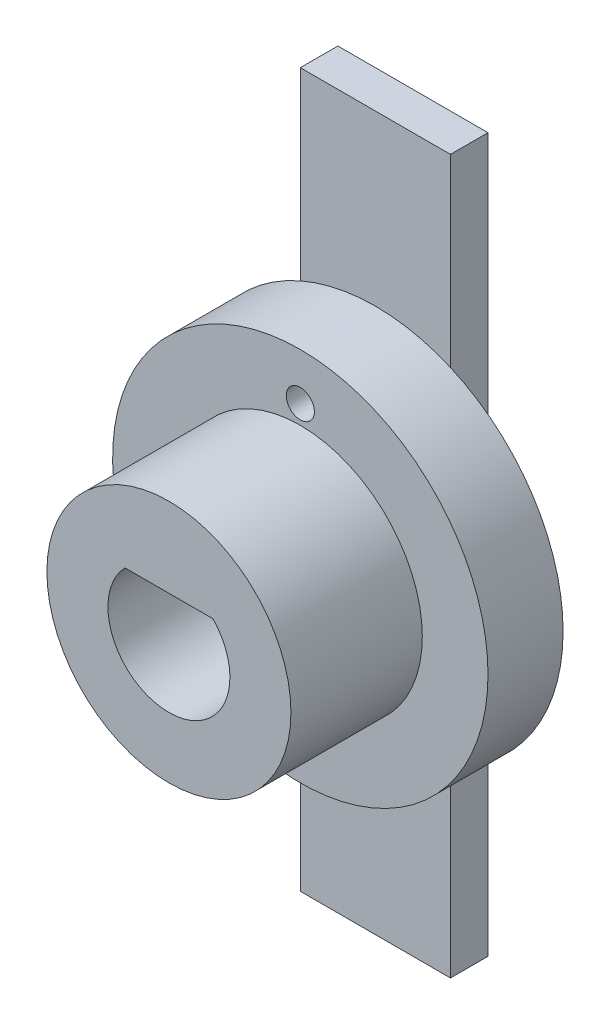
SolidWorks part; units mm, degrees
ref_plane "Plan de face" through (0, 0, 0) normal (0, 0, 1) x (1, 0, 0)
ref_plane "Plan de dessus" through (0, 0, 0) normal (0, 1, 0) x (1, 0, 0)
ref_plane "Plan de droite" through (0, 0, 0) normal (1, 0, 0) x (0, 0, -1)
sketch "Esquisse1" plane through (0, 0, 0) normal (0, 0, 1) x (1, 0, 0)
  line L8 (0, -7.5) -> (0, 7.5) construction
  circle A2 centre (0, -7.5) radius 0.75
  circle A3 centre (0, 7.5) radius 0.75
  circle A4 centre (0, 0) radius 10
  point P6 (0, 0)
  dimension "D2" = 1.5
  dimension "D3" = 1.5
  dimension "D4" = 20
  dimension "D1" = 15
extrude "Boss.-Extru.1" add sketch "Esquisse1" along normal blind 4
sketch "Esquisse2" [suppressed] plane through (0, 0, 10) normal (0, 0, 1) x (1, 0, 0)
  line L0 (-2.2, -2.0396) -> (-2.2, 2.0396)
  line L1 (3, -1.1913) -> (3, 1.3119) construction
  arc A0 (-2.2, -2.0396) -> (-2.2, 2.0396) centre (0, 0) ccw
  dimension "D1" = 6
  dimension "D2" = 5.2
extrude "Enlèv. mat.-Extru.1" [suppressed] cut sketch "Esquisse2" against normal offset from surface (8 mm away) 2 up to face at (10, 0, 0)
sketch "Esquisse3" plane through (0, 0, 4) normal (0, 0, 1) x (1, 0, 0)
  line L0 (-2.3452, 2.25) -> (2.3452, 2.25)
  line L1 (-0.8426, -3.25) -> (1.2459, -3.25) construction
  circle A0 centre (0, 0) radius 6.5
  arc A1 (-2.3452, 2.25) -> (2.3452, 2.25) centre (0, 0) ccw
  dimension "D1" = 6.5
  dimension "D3" = 13
  dimension "D2" = 5.5
extrude "Boss.-Extru.2" add sketch "Esquisse3" along normal blind 7
sketch "Esquisse5" plane through (0, 0, 4) normal (0, 0, 1) x (1, 0, 0)
  line L1 (2.3452, 2.25) -> (-2.3452, 2.25)
  line L2 (2.3452, 2.25) -> (-2.3452, 2.25)
  arc A1 (-2.3452, 2.25) -> (2.3452, 2.25) centre (0, 0) ccw
  arc A2 (-2.3452, 2.25) -> (2.3452, 2.25) centre (0, 0) ccw
  dimension "D1" = 0
extrude "Enlèv. mat.-Extru.2" cut sketch "Esquisse5" against normal offset from surface (2 mm away) 2 up to face at (10, 0, 0)
sketch "Esquisse4" plane through (0, 0, 0) normal (0, 0, -1) x (-1, 0, 0)
  line L1 (-4, 19) -> (4, 19)
  line L2 (-4, 19) -> (-4, -19)
  line L3 (-4, -19) -> (4, -19)
  line L4 (4, 19) -> (4, -19)
  point P4 (0, 19)
  point P5 (-4, 0)
  dimension "D1" = 8
  dimension "D2" = 38
extrude "Boss.-Extru.3" add sketch "Esquisse4" along normal blind 2
